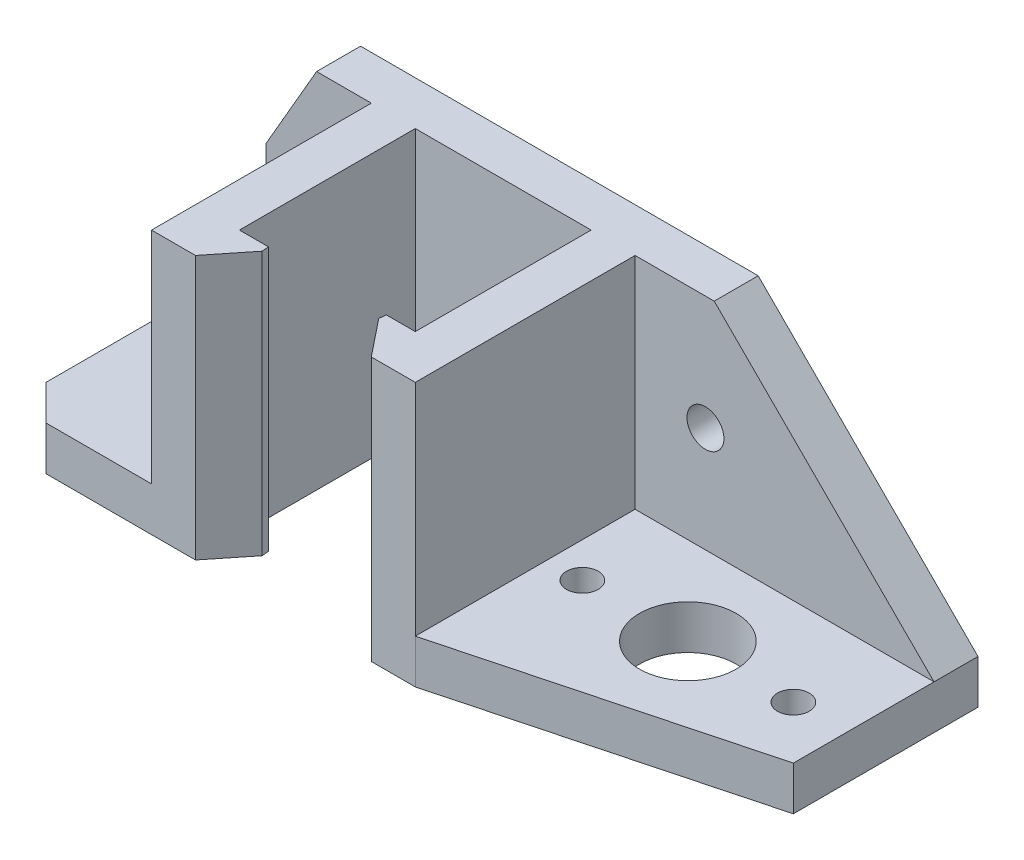
SolidWorks part; units mm, degrees
ref_plane "Front Plane" through (0, 0, 0) normal (0, 0, 1) x (1, 0, 0)
ref_plane "Top Plane" through (0, 0, 0) normal (0, 1, 0) x (1, 0, 0)
ref_plane "Right Plane" through (0, 0, 0) normal (1, 0, 0) x (0, 0, -1)
sketch "Sketch1" plane through (0, 0, 0) normal (0, 1, 0) x (1, 0, 0)
  line L1 (-15, 15) -> (15, 15)
  line L2 (-15, 15) -> (-15, -15)
  line L3 (-15, -15) -> (15, -15)
  line L4 (15, 15) -> (15, -15)
  dimension "D1" = 30
  dimension "D2" = 30
  dimension "D3" = 15
  dimension "D4" = 15
extrude "Boss-Extrude1" add sketch "Sketch1" along normal blind 30
sketch "Sketch2" plane through (0, 30, 0) normal (0, 1, 0) x (1, 0, 0)
  line L0 (-15, 15) -> (-15, -15) construction
  line L1 (-10, 10) -> (10, 10)
  line L2 (-10, 10) -> (-10, -10)
  line L3 (-10, -10) -> (10, -10)
  line L4 (10, 10) -> (10, -10)
  line L5 (15, 15) -> (-15, 15) construction
  dimension "D1" = 20
  dimension "D2" = 20
  dimension "D3" = 5
  dimension "D4" = 5
extrude "Cut-Extrude1" cut sketch "Sketch2" against normal through all
sketch "Sketch3" plane through (15, 0, 0) normal (1, 0, 0) x (0, 0, -1)
  line L0 (15, 30) -> (15, 0) construction
  line L1 (-15, 0) -> (15, 0)
  line L2 (-15, 0) -> (-15, 5)
  line L3 (-15, 5) -> (15, 5)
  line L4 (15, 0) -> (15, 5)
  dimension "D1" = 5
extrude "Boss-Extrude2" add sketch "Sketch3" along normal blind 40
sketch "Sketch4" plane through (0, 0, 0) normal (0, -1, 0) x (1, 0, 0)
  line L0 (10, 10) -> (10, -10) construction
  line L1 (-10, 10) -> (10, 10) construction
  circle A0 centre (31, 0) radius 5.5
  circle A1 centre (19, 0) radius 1.8
  circle A2 centre (43, 0) radius 1.8
  dimension "D2" = 11
  dimension "D3" = 3.6
  dimension "D4" = 3.6
  dimension "D1" = 21
  dimension "D5" = 10
  dimension "D6" = 10
  dimension "D7" = 10
  dimension "D8" = 12
  dimension "D9" = 12
extrude "Cut-Extrude2" cut sketch "Sketch4" against normal through all
sketch "Sketch7" plane through (0, 5, 0) normal (0, 1, 0) x (1, 0, 0)
  line L0 (15, -15) -> (49, -6)
  line L1 (49, -6) -> (49, 15)
  line L2 (55, 15) -> (15, 15) construction
  line L3 (49, 15) -> (55, 15)
  line L4 (55, 15) -> (55, -15)
  line L5 (55, 15) -> (55, -15) construction
  line L6 (55, -15) -> (15, -15) construction
  line L7 (55, -15) -> (15, -15)
  circle A0 centre (43, 0) radius 1.8 construction
  dimension "D1" = 6
  dimension "D2" = 6
extrude "Cut-Extrude3" cut sketch "Sketch7" against normal through all
sketch "Sketch5" plane through (15, 0, 0) normal (1, 0, 0) x (0, 0, -1)
  line L0 (15, 5) -> (-15, 5) construction
  line L1 (15, 30) -> (10, 30)
  line L2 (15, 30) -> (15, 5)
  line L3 (15, 5) -> (10, 5)
  line L4 (10, 30) -> (10, 5)
  dimension "D1" = 5
extrude "Boss-Extrude4" add sketch "Sketch5" along normal up to surface (34 mm away) up to face at (49, 2.5, -4.5)
chamfer "Chamfer1" distance 25 angle 45 1 edges at (49, 30, -12.5)
sketch "Sketch8" plane through (0, 0, -10) normal (0, 0, 1) x (1, 0, 0)
  line L0 (15, 30) -> (15, 5) construction
  line L1 (24, 30) -> (15, 30) construction
  circle A0 centre (23, 17) radius 2.1
  dimension "D1" = 4.2
  dimension "D2" = 8
  dimension "D3" = 13
extrude "Cut-Extrude4" cut sketch "Sketch8" against normal through all
sketch "Sketch9" plane through (-15, 0, 0) normal (-1, 0, 0) x (0, 0, 1)
  line L0 (-15, 0) -> (15, 0) construction
  line L1 (-15, 30) -> (-10, 30)
  line L2 (-15, 30) -> (-15, 0)
  line L3 (-15, 0) -> (-10, 0)
  line L4 (-10, 30) -> (-10, 0)
  dimension "D1" = 5
extrude "Boss-Extrude5" add sketch "Sketch9" along normal blind 12
chamfer "Chamfer2" distance 10 angle 30 1 edges at (-27, 30, -12.5) first distance on face at (-27, 15, -12.5)
sketch "Sketch10" plane through (0, 0, -10) normal (0, 0, 1) x (1, 0, 0)
  line L0 (-21.2265, 30) -> (-15, 30) construction
  line L1 (-15, 0) -> (-15, 30) construction
  circle A0 centre (-21, 17) radius 2.1
  dimension "D1" = 4.2
  dimension "D2" = 13
  dimension "D3" = 6
extrude "Cut-Extrude5" cut sketch "Sketch10" against normal through all
sketch "Sketch11" plane through (-15, 0, 0) normal (-1, 0, 0) x (0, 0, 1)
  line L0 (-10, 0) -> (-10, 30) construction
  line L1 (15, 0) -> (-10, 0)
  line L2 (15, 0) -> (15, 5)
  line L3 (15, 5) -> (-10, 5)
  line L4 (-10, 0) -> (-10, 5)
  dimension "D1" = 5
extrude "Boss-Extrude6" add sketch "Sketch11" along normal blind 16
chamfer "Chamfer3" distance 4 angle 45 2 edges at (-31, 2.5, 15) (-31, 2.5, -10)
sketch "Sketch12" plane through (0, 5, 0) normal (0, 1, 0) x (1, 0, 0)
  line L0 (-27, 10) -> (-15, 10) construction
  line L1 (-31, -11) -> (-31, 6) construction
  circle A0 centre (-25, 0) radius 1.8
  dimension "D1" = 3.6
  dimension "D2" = 10
  dimension "D3" = 6
extrude "Cut-Extrude6" cut sketch "Sketch12" against normal through all
sketch "Sketch13" plane through (0, 5, 0) normal (0, 1, 0) x (1, 0, 0)
  line L1 (-25, -3.4641) -> (-22, -1.7321)
  line L2 (-22, -1.7321) -> (-22, 1.7321)
  line L3 (-22, 1.7321) -> (-25, 3.4641)
  line L4 (-25, 3.4641) -> (-28, 1.7321)
  line L5 (-28, 1.7321) -> (-28, -1.7321)
  line L6 (-28, -1.7321) -> (-25, -3.4641)
  circle A0 centre (-25, 0) radius 3 construction
  dimension "D1" = 6
extrude "Cut-Extrude7" cut sketch "Sketch13" against normal blind 3
sketch "Sketch14" plane through (0, 30, 0) normal (0, 1, 0) x (1, 0, 0)
  line L0 (-6, -10) -> (-10, -15)
  line L1 (-10, -10) -> (10, -10) construction
  line L2 (-15, -15) -> (15, -15) construction
  line L3 (-10, -15) -> (10, -15)
  line L4 (10, -15) -> (6, -10)
  line L5 (6, -10) -> (-6, -10)
  line L6 (10, -10) -> (10, 10) construction
  dimension "D1" = 12
  dimension "D2" = 4
  dimension "D3" = 20
extrude "Cut-Extrude8" cut sketch "Sketch14" against normal through all
chamfer "Chamfer4" distance 1 angle 45 2 edges at (-6, 15, 10) (6, 15, 10) first distance on face at (-8, 15, 12.5) first distance on face at (8, 15, 12.5)
